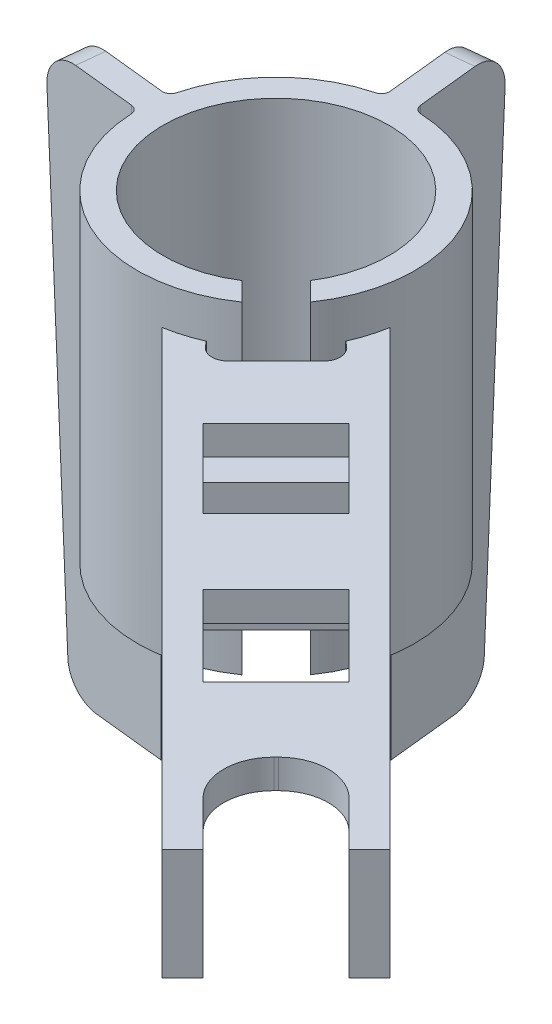
SolidWorks part; units mm, degrees
material "Nylon 101"
ref_plane "Front Plane" through (0, 0, 0) normal (0, 0, 1) x (1, 0, 0)
ref_plane "Top Plane" through (0, 0, 0) normal (0, 1, 0) x (1, 0, 0)
ref_plane "Right Plane" through (0, 0, 0) normal (1, 0, 0) x (0, 0, -1)
sketch "Sketch1" plane through (0, 0, 0) normal (0, 1, 0) x (1, 0, 0)
  line L0 (0, 9.969) -> (0, -10.0075) construction
  line L1 (0, 0) -> (-11.6167, 11.6167) construction
  line L2 (32.264, -3.3911) -> (14.8017, -1.5557) construction
  line L3 (-7.4145, 1.2066) -> (-4.4306, 0.893)
  line L4 (-7.4145, 1.2066) -> (-7.5033, 0.3613)
  line L5 (-7.5033, 0.3613) -> (-4.5194, 0.0477)
  line L6 (-0.3613, 7.5033) -> (-0.0477, 4.5194)
  line L7 (-1.2066, 7.4145) -> (-0.3613, 7.5033)
  line L8 (-1.2066, 7.4145) -> (-0.893, 4.4306)
  line L9 (3.5709, -2.5102) -> (2.5102, -3.5709) construction
  line L10 (3.5243, -2.4636) -> (2.9477, -1.8871)
  line L11 (2.4636, -3.5243) -> (1.8871, -2.9477)
  arc A0 (2.9477, -1.8871) -> (1.8871, -2.9477) centre (0, 0) ccw
  arc A1 (-4.2958, -0.1899) -> (2.4636, -3.5243) centre (0, 0) ccw
  arc A2 (-1.0789, 4.1624) -> (-4.1624, 1.0789) centre (0, 0) ccw
  circle A3 centre (0, 0) radius 4.3 construction
  arc A4 (0.1899, 4.2958) -> (-0.0477, 4.5194) centre (0.201, 4.5456) cw
  arc A5 (-0.893, 4.4306) -> (-1.0789, 4.1624) centre (-1.1416, 4.4044) cw
  arc A6 (-4.2958, -0.1899) -> (-4.5194, 0.0477) centre (-4.5456, -0.201) ccw
  arc A7 (-4.1624, 1.0789) -> (-4.4306, 0.893) centre (-4.4044, 1.1416) cw
  arc A8 (3.5243, -2.4636) -> (0.1899, 4.2958) centre (0, 0) ccw
  circle A9 centre (0, 0) radius 3.5 construction
  point P10 (-4.2764, 0.4495)
  point P13 (-7.4589, 0.784)
  point P17 (4.3, 0)
  point P24 (-0.0246, 4.2999)
  point P27 (-0.8699, 4.2111)
  point P30 (-4.2999, 0.0246)
  point P33 (-4.2111, 0.8699)
  point P36 (3.0406, -3.0406)
  point P37 (3.3471, 1.0233)
  dimension "D1" = 7
  dimension "D7" = 0.25
  dimension "D3" = 45
  dimension "D4" = 39
  dimension "D5" = 3.2
  dimension "D6" = 0.85
  dimension "D8" = 1.5
  dimension "D2" = 0.8
extrude "Boss-Extrude1" add sketch "Sketch1" against normal blind 10
ref_plane "Plane1" through (0, -8.25, 0) normal (0, -1, 0) x (-1, 0, 0)
sketch "Sketch2" plane through (0, -8.25, 0) normal (0, -1, 0) x (-1, 0, 0)
  line L0 (-1.8871, -2.9477) -> (-1.156, -2.2167)
  line L1 (-2.9477, -1.8871) -> (-2.2167, -1.156)
  line L2 (-2.9477, -1.8871) -> (-3.5243, -2.4636) construction
  line L3 (-2.4636, -3.5243) -> (-1.8871, -2.9477) construction
  arc A0 (-1.8871, -2.9477) -> (-2.9477, -1.8871) centre (0, 0) ccw
  arc A1 (-1.8871, -2.9477) -> (-2.9477, -1.8871) centre (0, 0) ccw construction
  arc A2 (-1.156, -2.2167) -> (-2.2167, -1.156) centre (0, 0) ccw
  circle A4 centre (0, 0) radius 3.5 construction
  circle A5 centre (0, 0) radius 2.5 construction
  point P1 (2.5, 0)
  point P18 (3.3471, 1.0233)
  dimension "D1" = 1
extrude "Boss-Extrude2" add sketch "Sketch2" along normal blind 1
sketch "Sketch3" plane through (0, -10, 0) normal (0, -1, 0) x (1, 0, 0)
  line L0 (-7.5033, -0.3613) -> (-3.4995, 0.0595)
  line L1 (-7.5033, -0.3613) -> (-7.4145, -1.2066)
  line L2 (-7.4145, -1.2066) -> (-3.4106, -0.7858)
  line L3 (-4.4306, -0.893) -> (-7.4145, -1.2066) construction
  line L4 (-7.5033, -0.3613) -> (-4.5194, -0.0477) construction
  line L5 (-1.2066, -7.4145) -> (-0.7858, -3.4106)
  line L6 (-1.2066, -7.4145) -> (-0.3613, -7.5033)
  line L7 (-0.3613, -7.5033) -> (0.0595, -3.4995)
  line L8 (-0.0477, -4.5194) -> (-0.3613, -7.5033) construction
  line L9 (-1.2066, -7.4145) -> (-0.893, -4.4306) construction
  arc A0 (-0.7858, -3.4106) -> (0.0595, -3.4995) centre (0, 0) ccw
  arc A1 (1.8871, 2.9477) -> (2.9477, 1.8871) centre (0, 0) ccw construction
  arc A2 (-3.4995, 0.0595) -> (-3.4106, -0.7858) centre (0, 0) ccw
extrude "Boss-Extrude3" add sketch "Sketch3" along normal blind 7
sketch "Sketch4" plane through (-0.0444, 0, 0.4227) normal (-0.1045, 0, 0.9945) x (0.9945, 0, 0.1045)
  line L0 (-4.4997, 0) -> (-6.4502, 0)
  line L1 (-3.4741, -17) -> (-5.7215, -17)
  line L2 (-3.4741, -17) -> (-7.5, -17) construction
  line L3 (-7.4491, -1.0485) -> (-6.7203, -16.0485)
  line L4 (-4.4997, 0) -> (-4.4997, 0.6425)
  line L5 (-4.4997, 0.6425) -> (-8.6362, 0.6425)
  line L6 (-8.6362, 0.6425) -> (-8.6362, -18.2376)
  line L7 (-8.6362, -18.2376) -> (-3.4741, -18.2376)
  line L8 (-3.4741, -18.2376) -> (-3.4741, -17)
  arc A0 (-6.4502, 0) -> (-7.4491, -1.0485) centre (-6.4502, -1) ccw
  arc A1 (-5.7215, -17) -> (-6.7203, -16.0485) centre (-5.7215, -16) cw
  point P8 (-7.5, 0)
  point P16 (-6.6741, -17)
  dimension "D1" = 1
  dimension "D3" = 1
  dimension "D2" = 3.2
extrude "Cut-Extrude1" cut sketch "Sketch4" against normal up to next
sketch "Sketch5" plane through (0.4227, 0, -0.0444) normal (0.9945, 0, -0.1045) x (-0.1045, 0, -0.9945)
  line L0 (4.4997, 0) -> (6.3982, 0)
  line L1 (7.4465, -1.1005) -> (6.7226, -16.0013)
  line L2 (7.5, -17) -> (3.4741, -17) construction
  line L3 (5.6743, -17) -> (3.4741, -17)
  line L4 (3.4741, -17) -> (3.4741, -17.9611)
  line L5 (3.4741, -17.9611) -> (9.6895, -17.9611)
  line L6 (9.6895, -17.9611) -> (9.5207, 0.6447)
  line L7 (9.5207, 0.6447) -> (4.4997, 0.6447)
  line L8 (4.4997, 0.6447) -> (4.4997, 0)
  arc A0 (6.7226, -16.0013) -> (5.6743, -17) centre (5.6743, -15.9504) cw
  arc A1 (7.4465, -1.1005) -> (6.3982, 0) centre (6.3982, -1.0496) ccw
  point P15 (6.6741, -17)
  point P18 (7.5, 0)
  dimension "D2" = 1.0496
  dimension "D1" = 3.2
extrude "Cut-Extrude2" cut sketch "Sketch5" against normal up to next
ref_plane "Plane2" through (3.0406, 0, 3.0406) normal (0.7071, 0, 0.7071) x (0.7071, 0, -0.7071)
sketch "Sketch6" plane through (3.0406, 0, 3.0406) normal (0.7071, 0, 0.7071) x (0.7071, 0, -0.7071)
  line L0 (0, 1.7775) -> (0, -12.799) construction
  line L1 (-8.0759, 0) -> (8.5257, 0) construction
  line L2 (-2.5, -1.2) -> (2.5, -1.2)
  line L3 (-2.5, -1.2) -> (-2.5, -4.65)
  line L4 (-2.5, -4.65) -> (2.5, -4.65)
  line L5 (2.5, -1.2) -> (2.5, -4.65)
  line L7 (-1.6, -2.1) -> (1.6, -2.1)
  line L8 (-1.6, -2.1) -> (-1.6, -3.75)
  line L9 (-1.6, -3.75) -> (1.6, -3.75)
  line L10 (1.6, -2.1) -> (1.6, -3.75)
  point P14 (0, -2.1)
  dimension "D1" = 0.9
  dimension "D2" = 0.9
  dimension "D3" = 0.9
  dimension "D4" = 3.2
  dimension "D5" = 1.65
  dimension "D6" = 1.2
  dimension "D7" = 0.9
extrude "Boss-Extrude4" add sketch "Sketch6" against normal up to surface and the other way blind 19 up to face at (-0.0287, -4.125, -0.0287)
sketch "Sketch7" plane through (0, -1.2, 0) normal (0, 1, 0) x (1, 0, 0)
  line L0 (2.4749, -2.4749) -> (16.4756, -16.4756) construction
  line L1 (18.2434, -14.7078) -> (14.7078, -18.2434) construction
  line L2 (15.3442, -17.607) -> (13.9654, -16.2281)
  line L3 (13.9654, -14.0361) -> (14.0361, -13.9654)
  line L4 (16.2281, -13.9654) -> (17.607, -15.3442)
  line L5 (17.607, -15.3442) -> (15.3442, -17.607)
  line L6 (8.3792, -10.642) -> (10.642, -8.3792)
  line L7 (10.642, -8.3792) -> (13.1168, -10.8541)
  line L8 (13.1168, -10.8541) -> (10.8541, -13.1168)
  line L9 (10.8541, -13.1168) -> (8.3792, -10.642)
  line L10 (3.9244, -6.1872) -> (6.1872, -3.9244)
  line L11 (6.1872, -3.9244) -> (8.5913, -6.3286)
  line L12 (8.5913, -6.3286) -> (6.3286, -8.5913)
  line L13 (6.3286, -8.5913) -> (3.9244, -6.1872)
  arc A0 (1.8871, -2.9477) -> (2.9477, -1.8871) centre (0, 0) ccw construction
  arc A1 (13.9654, -16.2281) -> (13.9654, -14.0361) centre (15.0614, -15.1321) cw
  arc A2 (16.2281, -13.9654) -> (14.0361, -13.9654) centre (15.1321, -15.0614) ccw
  point P9 (14.0007, -14.0007)
  point P14 (12.8693, -15.1321)
  point P17 (15.1321, -12.8693)
  point P20 (9.5106, -9.5106)
  point P25 (5.0558, -5.0558)
  dimension "D3" = 1.55
  dimension "D1" = 3.2
  dimension "D2" = 3.5
  dimension "D4" = 3.2
  dimension "D5" = 3.5
  dimension "D6" = 6.35
  dimension "D7" = 3.2
  dimension "D8" = 3.4
  dimension "D9" = 2.9
extrude "Cut-Extrude3" cut sketch "Sketch7" against normal up to next
sketch "Sketch8" plane through (0, -1.2, 0) normal (0, 1, 0) x (1, 0, 0)
  line L0 (2.4749, -2.4749) -> (16.4756, -16.4756) construction
  line L1 (15.3442, -17.607) -> (17.607, -15.3442) construction
  line L2 (1.8871, -2.9477) -> (2.4636, -3.5243)
  line L3 (2.9477, -1.8871) -> (3.5243, -2.4636)
  line L4 (2.6345, -4.1184) -> (4.1184, -2.6345)
  line L5 (1.895, -4.0826) -> (1.7628, -3.9221)
  line L6 (4.0826, -1.895) -> (3.9221, -1.7628)
  line L7 (6.1872, -3.9244) -> (3.9244, -6.1872) construction
  arc A0 (1.8871, -2.9477) -> (2.9477, -1.8871) centre (0, 0) ccw construction
  arc A1 (1.8871, -2.9477) -> (2.9477, -1.8871) centre (0, 0) ccw
  arc A2 (2.9477, -1.8871) -> (1.8871, -2.9477) centre (0, 0) ccw construction
  arc A3 (3.5243, -2.4636) -> (3.9221, -1.7628) centre (0, 0) ccw
  arc A4 (3.5243, -2.4636) -> (0.1899, 4.2958) centre (0, 0) ccw construction
  arc A5 (2.6345, -4.1184) -> (1.895, -4.0826) centre (2.281, -3.7648) cw
  arc A6 (4.1184, -2.6345) -> (4.0826, -1.895) centre (3.7648, -2.281) ccw
  arc A7 (1.7628, -3.9221) -> (2.4636, -3.5243) centre (0, 0) ccw
  point P25 (3.3764, -3.3764)
  point P32 (2.2451, -4.5078)
  point P35 (4.5078, -2.2451)
  dimension "D3" = 0.5
  dimension "D1" = 3.2
  dimension "D2" = 2.375
extrude "Cut-Extrude4" cut sketch "Sketch8" against normal up to surface (3.45 mm away) up to face at (6.1147, -4.65, 6.1147)
sketch "Sketch9" plane through (0, -4.65, 0) normal (0, -1, 0) x (1, 0, 0)
  line L0 (3.3764, 3.3764) -> (16.4756, 16.4756) construction
  line L1 (4.1184, 2.6345) -> (2.6345, 4.1184) construction
  line L2 (14.7078, 18.2434) -> (18.2434, 14.7078) construction
  line L3 (9.7581, 12.0208) -> (12.0208, 9.7581)
  line L4 (9.7581, 12.0208) -> (15.3442, 17.607)
  line L5 (12.0208, 9.7581) -> (17.607, 15.3442)
  line L6 (17.607, 15.3442) -> (15.3442, 17.607)
  line L7 (8.4853, 10.748) -> (10.748, 8.4853)
  line L8 (10.748, 8.4853) -> (8.2731, 6.0104)
  line L9 (8.2731, 6.0104) -> (6.0104, 8.2731)
  line L10 (6.0104, 8.2731) -> (8.4853, 10.748)
  line L11 (2.9522, 5.2149) -> (5.2149, 2.9522)
  line L12 (5.2149, 2.9522) -> (7.0004, 4.7376)
  line L13 (7.0004, 4.7376) -> (4.7376, 7.0004)
  line L14 (4.7376, 7.0004) -> (2.9522, 5.2149)
  dimension "D1" = 3.2
  dimension "D2" = 7.9
  dimension "D3" = 1.8
  dimension "D4" = 15
  dimension "D5" = 1.8
  dimension "D6" = 1
extrude "Cut-Extrude5" cut sketch "Sketch9" against normal up to next
